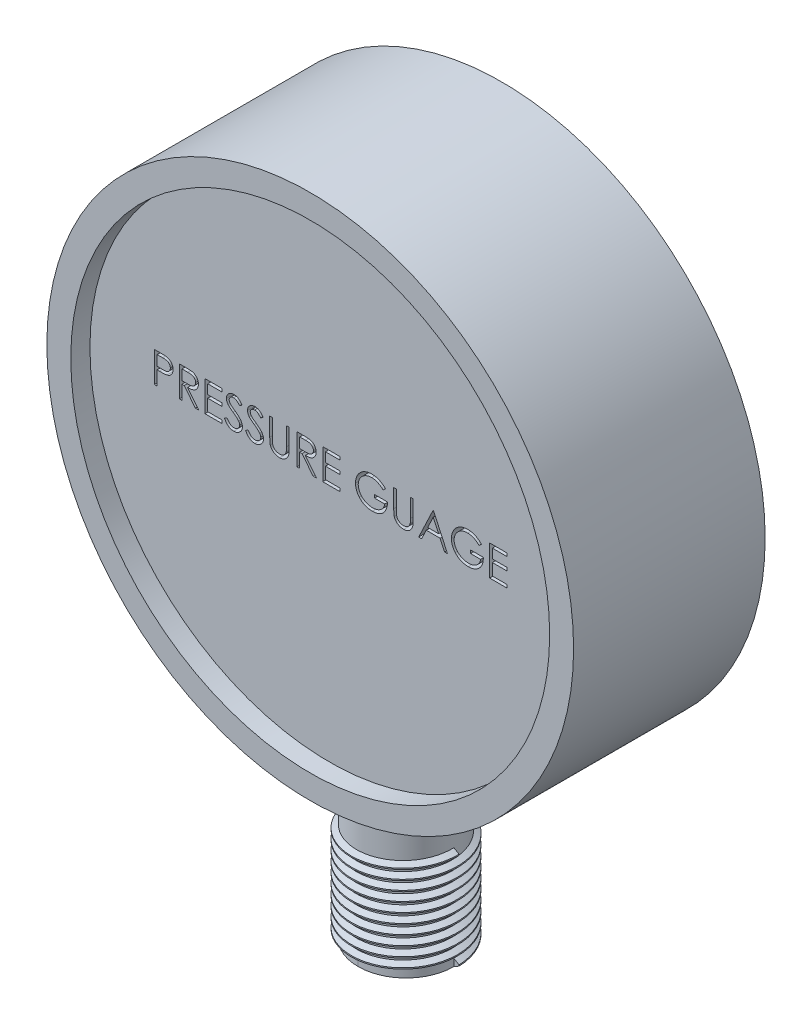
SolidWorks part; units mm, degrees
ref_plane "Front Plane" through (0, 0, 0) normal (0, 0, 1) x (1, 0, 0)
ref_plane "Top Plane" through (0, 0, 0) normal (0, 1, 0) x (1, 0, 0)
ref_plane "Right Plane" through (0, 0, 0) normal (1, 0, 0) x (0, 0, -1)
sketch "Sketch1" plane through (0, 0, 0) normal (0, 0, 1) x (1, 0, 0)
  circle A0 centre (0, 0) radius 27.5
  dimension "D1" = 55
extrude "Boss-Extrude1" add sketch "Sketch1" along normal blind 20
sketch "Sketch2" plane through (0, 0, 20) normal (0, 0, 1) x (1, 0, 0)
  circle A0 centre (0, 0) radius 25
  circle A1 centre (0, 0) radius 27.5 construction
  dimension "D1" = 2.5
extrude "Cut-Extrude1" cut sketch "Sketch2" against normal blind 2 contours A0
sketch "Sketch3" plane through (0, 0, 0) normal (0, 1, 0) x (1, 0, 0)
  circle A0 centre (0, -10) radius 5
  dimension "D1" = 10
extrude "Boss-Extrude3" add sketch "Sketch3" against normal blind 45
thread "Thread1" pitch 1 method extrude profile "Thread Profile1" start angle 0, offset 0, length 10, pitch 1, diameter 10
ref_plane "Plane1" through (5, -45, 10) normal (0, 0, 1) x (1, 0, 0)
sketch "Thread Profile1" plane through (5, -45, 10) normal (0, 0, 1) x (1, 0, 0)
  line L0 (0, 0) -> (0, 1) construction
  line L1 (0, 0) -> (0.5413, 0.3125)
  line L2 (0.5413, 0.3125) -> (0.5413, 0.4375)
  line L3 (0.5413, 0.4375) -> (0, 0.75)
  line L4 (0.5413, 0.375) -> (0, 0.375) construction
  line L11 (0, 0) -> (0, 0.75)
  point P2 (0, 0)
  dimension "Pitch" = 1
  dimension "Profile_Angle" = 60
  dimension "Profile_Land" = 0.125
  dimension "Profile_Height" = 0.5413
sketch "Sketch9" plane through (0, 0, 18) normal (0, 0, 1) x (1, 0, 0)
  line L0 (25, 0) -> (-25, 0) construction
  circle A0 centre (0, 0) radius 25 construction
  text T0 "PRESSURE GUAGE"
  point P8 (0, 0)
extrude "Cut-Extrude4" cut sketch "Sketch9" against normal blind 13
ref_axis "Axis1" through (0, -53.6683, 10) along (0, 1, 0)
